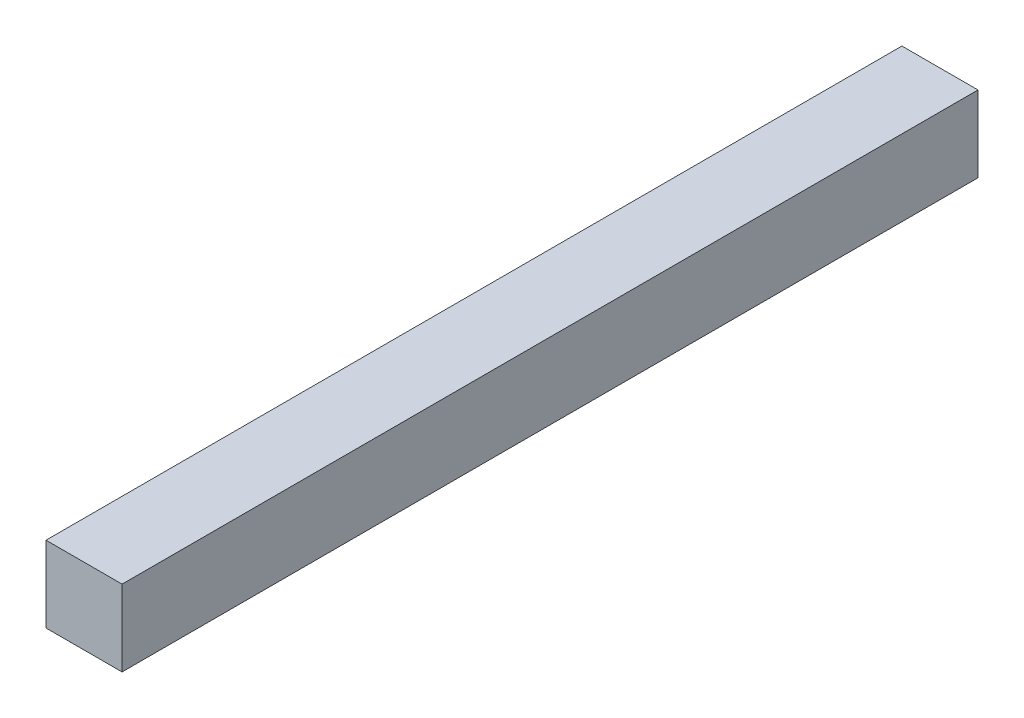
SolidWorks part; units mm, degrees
ref_plane "Plan de face" through (0, 0, 0) normal (0, 0, 1) x (1, 0, 0)
ref_plane "Plan de dessus" through (0, 0, 0) normal (0, 1, 0) x (1, 0, 0)
ref_plane "Plan de droite" through (0, 0, 0) normal (1, 0, 0) x (0, 0, -1)
sketch "Esquisse1" plane through (0, 0, 0) normal (0, 0, 1) x (1, 0, 0)
  line L1 (0, 0) -> (40, 0)
  line L2 (0, 0) -> (0, 40)
  line L3 (0, 40) -> (40, 40)
  line L4 (40, 0) -> (40, 40)
  dimension "D1" = 40
extrude "Boss.-Extru.1" add sketch "Esquisse1" along normal blind 450
